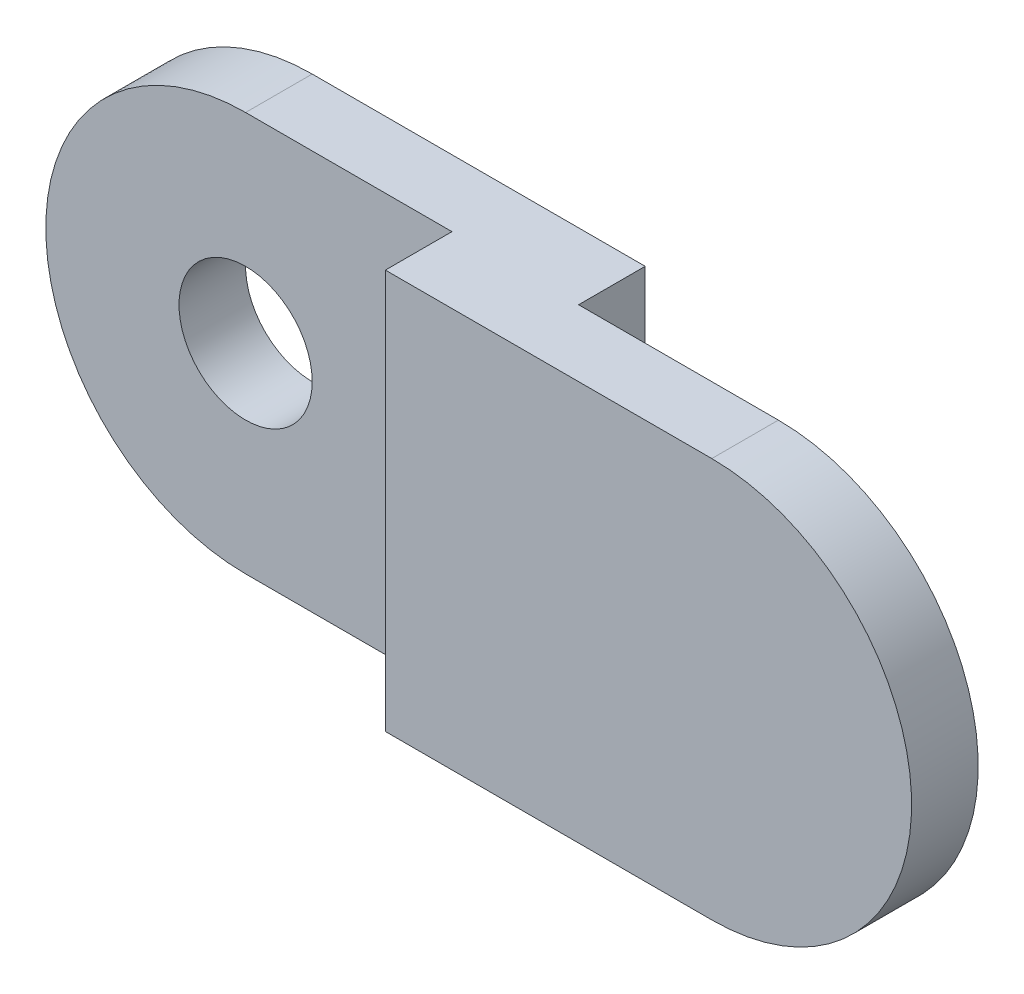
SolidWorks part; units mm, degrees
ref_plane "Front Plane" through (0, 0, 0) normal (0, 0, 1) x (1, 0, 0)
ref_plane "Top Plane" through (0, 0, 0) normal (0, 1, 0) x (1, 0, 0)
ref_plane "Right Plane" through (0, 0, 0) normal (1, 0, 0) x (0, 0, -1)
sketch "Sketch1" plane through (0, 0, 0) normal (0, 0, 1) x (1, 0, 0)
  line L1 (0, 0) -> (20, 0)
  line L3 (0, 15) -> (20, 15)
  arc A0 (0, 15) -> (0, 0) centre (0, 7.5) ccw
  arc A1 (0, 0) -> (-3.4224, 0.8264) centre (0, 7.5) cw
  arc A2 (20, 15) -> (20, 0) centre (20, 7.5) cw
  dimension "D1" = 20
  dimension "D2" = 15
extrude "Boss-Extrude1" add sketch "Sketch1" along normal blind 5 contours A0 | L1 L3 region at (10, 7.5, 0)
sketch "Sketch6" plane through (0, 0, 0) normal (0, 0, -1) x (-1, 0, 0)
  line L0 (0, 0) -> (-20, 0) construction
  line L1 (0, 0) -> (-20, 0) construction
  line L2 (-20, 15) -> (-12.5, 15)
  line L8 (-20, 0) -> (-12.5, 0)
  line L9 (-12.5, 15) -> (-12.5, 0)
  arc A0 (-20, 15) -> (-20, 0) centre (-20, 7.5) ccw
extrude "Cut-Extrude2" cut sketch "Sketch6" against normal blind 2.5
sketch "Sketch7" plane through (0, 0, 5) normal (0, 0, 1) x (1, 0, 0)
  line L0 (0, 0) -> (20, 0) construction
  line L1 (0, 0) -> (20, 0) construction
  line L2 (0, 15) -> (7.7468, 15)
  line L4 (0, 0) -> (5, 0)
  line L5 (0, 0) -> (7.7468, 0)
  line L6 (7.7468, 15) -> (7.7468, 0)
  arc A0 (0, 15) -> (0, 0) centre (0, 7.5) ccw
  arc M1 (0, 15) -> (0, 0) centre (0, 7.5) ccw
extrude "Cut-Extrude6" cut sketch "Sketch7" against normal blind 2.5 contours M1 region at (0.8254, 7.5, 5)
sketch "Sketch11" plane through (0, 0, 2.5) normal (0, 0, 1) x (1, 0, 0)
  circle A0 centre (0, 7.5) radius 2.5
  dimension "D1" = 5
extrude "Cut-Extrude7" cut sketch "Sketch11" against normal blind 2.5
sketch "Sketch12" plane through (0, 0, 2.5) normal (0, 0, -1) x (-1, 0, 0)
  circle A0 centre (-20, 7.5) radius 2.5
  dimension "D1" = 5
extrude "Boss-Extrude3" add sketch "Sketch12" along normal blind 2.5 contours A0
ref_plane "Plane1" through (0, 0, -10) normal (0, 0, 1) x (1, 0, 0)
